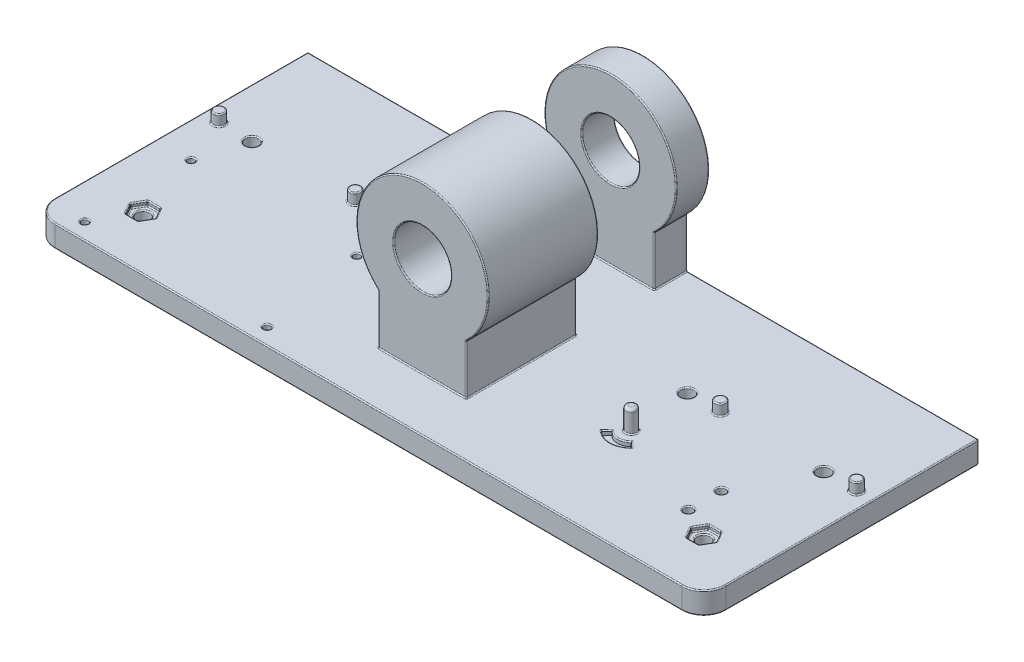
SolidWorks part; units mm, degrees
ref_plane "Front Plane" through (0, 0, 0) normal (0, 0, 1) x (1, 0, 0)
ref_plane "Top Plane" through (0, 0, 0) normal (0, 1, 0) x (1, 0, 0)
ref_plane "Right Plane" through (0, 0, 0) normal (1, 0, 0) x (0, 0, -1)
sketch "Sketch1" plane through (0, 0, 0) normal (0, 1, 0) x (1, 0, 0)
  line L0 (152.5, 125) -> (152.5, 0) construction
  line L1 (0, 0) -> (305, 0)
  line L2 (0, 0) -> (0, 125)
  line L3 (0, 125) -> (305, 125)
  line L4 (305, 0) -> (305, 125)
  line L5 (25, 100) -> (280, 100) construction
  line L6 (280, 25) -> (280, 100) construction
  line L7 (25, 25) -> (280, 25) construction
  line L8 (25, 25) -> (25, 100) construction
  line L9 (152.5, 62.5) -> (25, 62.5) construction
  line L10 (30.7735, 100) -> (27.8868, 105) construction
  line L11 (27.8868, 105) -> (22.1132, 105) construction
  line L12 (22.1132, 105) -> (19.2265, 100) construction
  line L13 (19.2265, 100) -> (22.1132, 95) construction
  line L14 (22.1132, 95) -> (27.8868, 95) construction
  line L15 (27.8868, 95) -> (30.7735, 100) construction
  line L16 (27.8868, 30) -> (30.7735, 25) construction
  line L17 (22.1132, 30) -> (27.8868, 30) construction
  line L18 (19.2265, 25) -> (22.1132, 30) construction
  line L19 (22.1132, 20) -> (19.2265, 25) construction
  line L20 (27.8868, 20) -> (22.1132, 20) construction
  line L21 (30.7735, 25) -> (27.8868, 20) construction
  line L22 (282.8868, 30) -> (277.1132, 30) construction
  line L23 (285.7735, 25) -> (282.8868, 30) construction
  line L24 (282.8868, 20) -> (285.7735, 25) construction
  line L25 (277.1132, 20) -> (282.8868, 20) construction
  line L26 (274.2265, 25) -> (277.1132, 20) construction
  line L27 (277.1132, 30) -> (274.2265, 25) construction
  line L28 (277.1132, 95) -> (274.2265, 100) construction
  line L29 (282.8868, 95) -> (277.1132, 95) construction
  line L30 (285.7735, 100) -> (282.8868, 95) construction
  line L31 (282.8868, 105) -> (285.7735, 100) construction
  line L32 (277.1132, 105) -> (282.8868, 105) construction
  line L33 (274.2265, 100) -> (277.1132, 105) construction
  line L34 (172.5, 75) -> (172.5, 125) construction
  line L35 (132.5, 0) -> (172.5, 0) construction
  line L36 (132.5, 0) -> (132.5, 125) construction
  line L37 (132.5, 125) -> (172.5, 125) construction
  line L38 (172.5, 0) -> (172.5, 125) construction
  line L39 (132.5, 75) -> (172.5, 75) construction
  line L40 (132.5, 75) -> (132.5, 25) construction
  line L41 (132.5, 25) -> (172.5, 25) construction
  line L42 (172.5, 75) -> (172.5, 25) construction
  line L50 (305, 14.5) -> (253.3, 14.5) construction
  line L51 (0, 84.5) -> (15, 69.5) construction
  line L52 (132.5, 75) -> (117.5, 60) construction
  line L53 (117.5, 60) -> (117.5, 85) construction
  line L54 (0, 125) -> (108, 125) construction
  line L55 (0, 125) -> (0, 84.5) construction
  line L56 (0, 84.5) -> (108, 84.5) construction
  line L57 (108, 125) -> (108, 84.5) construction
  line L58 (15, 69.5) -> (15, 84.5) construction
  line L59 (30, 84.5) -> (0, 84.5) construction
  line L60 (30, 84.5) -> (30, 69.5) construction
  line L61 (30, 69.5) -> (0, 69.5) construction
  line L62 (0, 84.5) -> (0, 69.5) construction
  line L63 (92, 84.5) -> (92, 69.5) construction
  line L64 (62, 0) -> (62, 125) construction
  line L65 (253.3, 14.5) -> (253.3, 0) construction
  line L66 (253.3, 38.75) -> (280.2, 38.75) construction
  line L67 (253.3, 14.5) -> (280.2, 14.5) construction
  line L68 (253.3, 14.5) -> (253.3, 63) construction
  line L69 (253.3, 63) -> (280.2, 63) construction
  line L70 (280.2, 14.5) -> (280.2, 63) construction
  line L71 (266.75, 31.25) -> (266.75, 38.75) construction
  circle A1 centre (25, 100) radius 5 construction
  circle A3 centre (280, 25) radius 3
  circle A4 centre (25, 25) radius 3
  circle A8 centre (117.5, 60) radius 3
  circle A9 centre (117.5, 85) radius 3
  circle A10 centre (7.5, 77) radius 3 construction
  circle A11 centre (22.5, 77) radius 3
  circle A12 centre (69.5, 77) radius 3 construction
  circle A13 centre (84.5, 77) radius 3
  circle A14 centre (220.5, 77) radius 3
  circle A15 centre (235.5, 77) radius 3 construction
  circle A16 centre (282.5, 77) radius 3
  circle A17 centre (297.5, 77) radius 3 construction
  circle A18 centre (266.75, 31.25) radius 2
  circle A19 centre (266.75, 46.25) radius 2
  dimension "D3" = 6
  dimension "D22" = 4
  dimension "D1" = 305
  dimension "D2" = 125
  dimension "D5" = 10
  dimension "D6" = 40
  dimension "D8" = 50
  dimension "D12" = 15
  dimension "D7" = 40.5
  dimension "D9" = 108
  dimension "D10" = 15
  dimension "D11" = 30
  dimension "D15" = 62
  dimension "D16" = 15
  dimension "D17" = 25
  dimension "D18" = 51.7
  dimension "D19" = 14.5
  dimension "D20" = 26.9
  dimension "D21" = 48.5
  dimension "D23" = 7.5
  dimension "D4" = 25
  dimension "D13" = 2
  dimension "D14" = 2
extrude "Boss-Extrude1" add sketch "Sketch1" along normal blind 10
sketch "Sketch7" plane through (0, 10, 0) normal (0, 1, 0) x (1, 0, 0)
  line L0 (0, 0) -> (305, 0) construction
  line L1 (132.5, 24.5) -> (172.5, 24.5)
  line L2 (132.5, 24.5) -> (132.5, 74.5)
  line L3 (132.5, 74.5) -> (172.5, 74.5)
  line L4 (172.5, 24.5) -> (172.5, 74.5)
  line L5 (152.5, 0) -> (152.5, 125) construction
  line L6 (305, 125) -> (0, 125) construction
  line L18 (132.5, 110) -> (172.5, 110)
  line L19 (132.5, 110) -> (132.5, 125)
  line L20 (132.5, 125) -> (172.5, 125)
  line L21 (172.5, 110) -> (172.5, 125)
  point P11 (152.5, 74.5)
  point P20 (152.5, 110)
  dimension "D1" = 40
  dimension "D2" = 50
  dimension "D4" = 15
  dimension "D3" = 35.5
extrude "Boss-Extrude2" add sketch "Sketch7" along normal blind 22.6393
sketch "Sketch11" plane through (0, 0, -24.5) normal (0, 0, 1) x (1, 0, 0)
  circle A0 centre (152.5, 55) radius 30
  circle A1 centre (152.5, 55) radius 13
  dimension "D1" = 60
  dimension "D2" = 26
extrude "Boss-Extrude3" add sketch "Sketch11" against normal up to surface (100.5 mm away) up to face at (152.5, 13.1598, -125)
ref_plane "Plane1" through (0, 0, -62.5) normal (0, 0, 1) x (1, 0, 0)
sketch "Sketch12" plane through (305, 0, 0) normal (1, 0, 0) x (0, 0, -1)
  line L0 (125, 85) -> (24.5, 85) construction
  line L1 (74.5, 10) -> (110, 10)
  line L2 (74.5, 10) -> (74.5, 85)
  line L3 (74.5, 85) -> (110, 85)
  line L4 (110, 10) -> (110, 85)
  line L6 (110, 32.6393) -> (110, 10) construction
extrude "Cut-Extrude2" cut sketch "Sketch12" against normal through all
sketch "Sketch13" plane through (0, 10, 0) normal (0, 1, 0) x (1, 0, 0)
  line L0 (222.5, 49.5) -> (172.5, 49.5) construction
  line L1 (172.5, 24.5) -> (172.5, 74.5) construction
  circle A1 centre (222.5, 49.5) radius 2.4
  dimension "D1" = 4.8
  dimension "D2" = 50
extrude "Boss-Extrude4" add sketch "Sketch13" along normal blind 10
sketch "Sketch6" plane through (0, 10, 0) normal (0, 1, 0) x (1, 0, 0)
  line L0 (152.5, 125) -> (152.5, 0) construction
  line L7 (215.7825, 42.7825) -> (218.0806, 45.0806)
  line L8 (0, 0) -> (305, 0) construction
  line L9 (152.5, 62.5) -> (0, 62.5) construction
  line L10 (0, 125) -> (0, 0) construction
  line L29 (27.8868, 30) -> (30.7735, 25)
  line L30 (274.2265, 25) -> (277.1132, 20)
  line L31 (277.1132, 20) -> (282.8868, 20)
  line L32 (282.8868, 20) -> (285.7735, 25)
  line L33 (285.7735, 25) -> (282.8868, 30)
  line L34 (282.8868, 30) -> (277.1132, 30)
  line L35 (277.1132, 30) -> (274.2265, 25)
  line L36 (22.1132, 30) -> (27.8868, 30)
  line L37 (19.2265, 25) -> (22.1132, 30)
  line L38 (22.1132, 20) -> (19.2265, 25)
  line L39 (27.8868, 20) -> (22.1132, 20)
  line L40 (30.7735, 25) -> (27.8868, 20)
  line L41 (231.3388, 40.6612) -> (213.6612, 58.3388) construction
  line L42 (213.6612, 40.6612) -> (231.3388, 58.3388) construction
  line L43 (222.5, 49.5) -> (222.5, 37) construction
  line L44 (213.6612, 40.6612) -> (222.5, 37) construction
  line L45 (222.5, 37) -> (231.3388, 40.6612) construction
  line L46 (229.2175, 42.7825) -> (226.9194, 45.0806)
  circle A0 centre (280, 25) radius 5 construction
  circle A1 centre (222.5, 49.5) radius 12.5 construction
  circle A2 centre (222.5, 49.5) radius 9.5 construction
  circle A3 centre (222.5, 49.5) radius 6.25 construction
  arc A4 (218.0806, 45.0806) -> (226.9194, 45.0806) centre (222.5, 49.5) ccw
  arc A5 (215.7825, 42.7825) -> (229.2175, 42.7825) centre (222.5, 49.5) ccw
  dimension "D2" = 25
  dimension "D4" = 12.5
  dimension "D1" = 10
  dimension "D3" = 3
extrude "Cut-Extrude1" cut sketch "Sketch6" against normal blind 2
fillet "Fillet1" radius 1.3 1 edges at (222.5, 20, -47.1)
sketch "Sketch15" plane through (0, 10, 0) normal (0, 1, 0) x (1, 0, 0)
  line L0 (69.5, 77) -> (7.5, 77) construction
  line L1 (38.5, 77) -> (38.5, 84.5) construction
  line L2 (0, 84.5) -> (108, 84.5) construction
  line L3 (152.5, 125) -> (152.5, 0) construction
  circle A1 centre (69.5, 77) radius 2.5
  circle A2 centre (7.5, 77) radius 2.5
  circle A3 centre (7.5, 77) radius 2.5
  circle A4 centre (235.5, 77) radius 2.5
  circle A5 centre (297.5, 77) radius 2.5
  dimension "D1" = 0.5
extrude "Boss-Extrude5" add sketch "Sketch15" along normal blind 5
sketch "Sketch16" plane through (0, 10, 0) normal (0, 1, 0) x (1, 0, 0)
  line L0 (0, 0) -> (305, 0) construction
  line L1 (0, 125) -> (0, 0) construction
  circle A0 centre (16, 7.5) radius 1.55
  circle A1 centre (98.95, 7.5) radius 1.55
  circle A2 centre (16, 55.866) radius 1.55
  circle A3 centre (91.33, 55.866) radius 1.55
  point P10 (0, 0)
  dimension "D1" = 3.1
  dimension "D2" = 7.5
  dimension "D3" = 82.95
  dimension "D4" = 16
  dimension "D5" = 48.366
  dimension "D6" = 75.33
extrude "Cut-Extrude3" cut sketch "Sketch16" against normal through all
chamfer "Chamfer1" distance 3.3 angle 45 6 edges at (282.5, 0, -74) (220.5, 0, -74) (84.5, 0, -80) (22.5, 0, -80) (117.5, 0, -57) (117.5, 0, -82)
fillet "Fillet3" radius 10 2 edges at (305, 5, 0) (0, 5, 0)
fillet "Fillet2" radius 0.5 107 edges at (25, 0, -28) (19.2265, 9, -25) (22.1132, 9, -20) (27.8868, 9, -30) (22.1132, 9, -30) (27.8868, 9, -20) (30.7735, 9, -25) (29.3301, 8, -27.5) (29.3301, 8, -22.5) (25, 8, -20) (20.6699, 8, -22.5) (20.6699, 8, -27.5) (25, 8, -30) (25, 8, -28) (280, 0, -22) (277.1132, 9, -30) (274.2265, 9, -25) (285.7735, 9, -25) (282.8868, 9, -30) (277.1132, 9, -20) (282.8868, 9, -20) (280, 8, -30) (284.3301, 8, -27.5) (284.3301, 8, -22.5) (280, 8, -20) (275.6699, 8, -22.5) (275.6699, 8, -27.5) (280, 8, -22) (235.5, 15, -74.5) (297.5, 15, -79.5) (69.5, 15, -79.5) (7.5, 15, -74.5) (117.5, 10, -57) (280, 10, -20) (284.3301, 10, -22.5) (284.3301, 10, -27.5) (280, 10, -30) (275.6699, 10, -27.5) (275.6699, 10, -22.5) (20.6699, 10, -22.5) (25, 10, -20) (29.3301, 10, -22.5) (29.3301, 10, -27.5) (25, 10, -30) (20.6699, 10, -27.5) (117.5, 10, -82) (305, 10, -67.5) (152.5, 10, 0) (0, 10, -67.5) (22.5, 10, -80) (84.5, 10, -80) (220.5, 10, -74) (282.5, 10, -74) (222.5, 10, -51.9) (7.5, 10, -79.5) (69.5, 10, -79.5) (235.5, 10, -79.5) (297.5, 10, -79.5) (165.5, 55, -24.5) (152.5, 10, -24.5) (152.5, 85, -24.5) (132.5, 32.6393, -49.5) (132.5, 21.3197, -24.5) (132.5, 10, -49.5) (165.5, 55, -74.5) (152.5, 10, -74.5) (152.5, 85, -74.5) (132.5, 21.3197, -74.5) (172.5, 21.3197, -24.5) (172.5, 32.6393, -49.5) (172.5, 21.3197, -74.5) (172.5, 10, -49.5) (172.5, 32.6393, -117.5) (172.5, 10, -117.5) (132.5, 32.6393, -117.5) (132.5, 10, -117.5) (165.5, 55, -125) (66.25, 10, -125) (0, 5, -125) (152.5, 0, -125) (305, 5, -125) (238.75, 10, -125) (172.5, 21.3197, -125) (152.5, 85, -125) (132.5, 21.3197, -125) (139.5, 55, -110) (152.5, 10, -110) (132.5, 21.3197, -110) (152.5, 85, -110) (172.5, 21.3197, -110) (305, 0, -67.5) (152.5, 0, 0) (0, 0, -67.5) (222.5, 10, -43.25) (216.9315, 10, -43.9315) (222.5, 10, -40) (228.0685, 10, -43.9315) (266.75, 10, -48.25) (266.75, 10, -29.25) (16, 10, -5.95) (91.33, 10, -54.316) (16, 10, -54.316) (98.95, 10, -5.95) (302.0711, 0, -2.9289) (2.9289, 0, -2.9289) (2.9289, 10, -2.9289) (302.0711, 10, -2.9289)
chamfer "Chamfer2" distance 1.65 4 edges at (98.95, 0, -5.95) (91.33, 0, -54.316) (16, 0, -5.95) (16, 0, -54.316)
equation "\"joint_width\"=4"
equation "\"short_base_length\"=12.5"
equation "\"D2@Sketch1\"=\"short_base_length\""
equation "\"outer_diam_main_joint\"=6"
equation "\"D1@Sketch11\"=\"outer_diam_main_joint\""
equation "\"D1@Sketch7\"=\"outer_diam_main_joint\"-2"
equation "\"D1@Boss-Extrude2\"=(\"outer_diam_main_joint\"/2)+1.5cm-sqr((\"outer_diam_main_joint\"/2)^2-((\"outer_diam_main_joint\"-2)/2)^2)"
equation "\"D6@Sketch1\"=\"outer_diam_main_joint\"-2"
equation "\"pulleyside\"=1.5"
